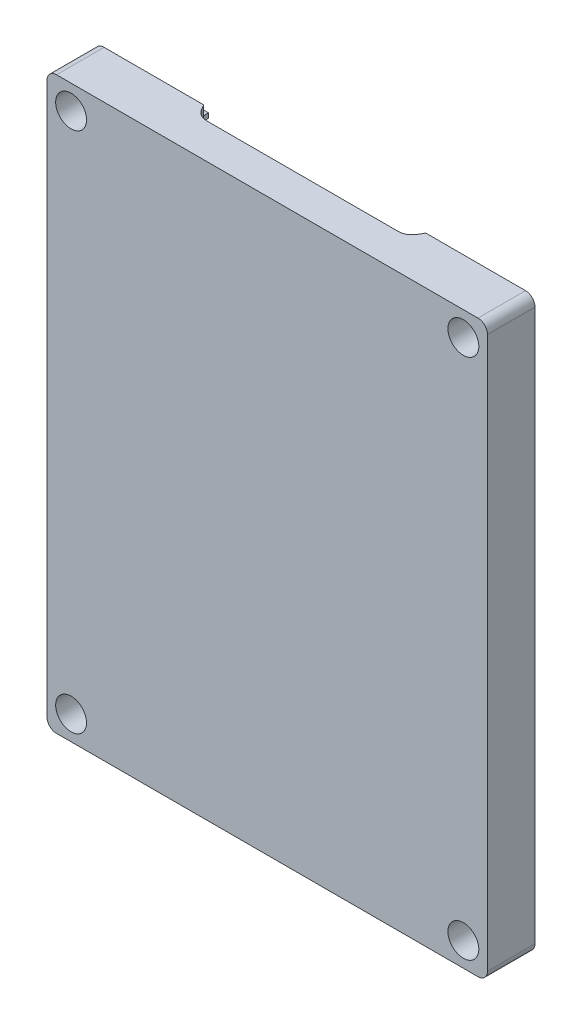
SolidWorks part; units mm, degrees
note: The reader was unsure of these and kept them because the rebuilt part matched: shared geometry of "Esquisse1<5>".
material "ABS"
ref_plane "Plan de face" through (0, 0, 0) normal (0, 0, 1) x (1, 0, 0)
ref_plane "Plan de dessus" through (0, 0, 0) normal (0, 1, 0) x (1, 0, 0)
ref_plane "Plan de droite" through (0, 0, 0) normal (1, 0, 0) x (0, 0, -1)
sketch "Esquisse1" plane through (0, 0, 0) normal (0, 0, 1) x (1, 0, 0)
  line L10 (-44.32, 60.43) -> (44.32, 60.43)
  line L11 (32.37, 58.48) -> (-32.37, 58.48)
  line L12 (-43.37, 46.0658) -> (-31.9558, 57.48)
  line L13 (31.9558, 57.48) -> (-31.9558, 57.48)
  line L14 (31.9558, 57.48) -> (43.37, 46.0658)
  line L15 (43.37, 46.0658) -> (43.37, -45.1658)
  line L21 (43.37, -45.1658) -> (31.9558, -56.58)
  line L26 (31.9558, -56.58) -> (-31.9558, -56.58)
  line L28 (-31.9558, -56.58) -> (-43.37, -45.1658)
  line L48 (-43.37, -45.1658) -> (-43.37, 46.0658)
  line L55 (-23.35, 60.43) -> (-44.32, 60.43)
  line L56 (-46.32, 58.43) -> (-46.32, -57.53)
  line L57 (-44.32, -59.53) -> (44.32, -59.53)
  line L58 (46.32, -57.53) -> (46.32, 58.43)
  line L59 (44.32, 60.43) -> (23.35, 60.43)
  line L64 (23.35, 60.43) -> (23.35, 58.48)
  line L65 (23.35, 58.48) -> (32.37, 58.48)
  line L66 (32.37, 58.48) -> (44.37, 46.48)
  line L67 (44.37, 46.48) -> (44.37, -45.58)
  line L68 (44.37, -45.58) -> (32.37, -57.58)
  line L69 (32.37, -57.58) -> (-32.37, -57.58)
  line L70 (-32.37, -57.58) -> (-44.37, -45.58)
  line L71 (-44.37, -45.58) -> (-44.37, 46.48)
  line L72 (-44.37, 46.48) -> (-32.37, 58.48)
  line L73 (-32.37, 58.48) -> (-23.35, 58.48)
  line L74 (-23.35, 58.48) -> (-23.35, 60.43)
  line L76 (-46.32, 58.43) -> (-46.32, -57.53)
  line L77 (-44.32, -59.53) -> (44.32, -59.53)
  line L78 (46.32, -57.53) -> (46.32, 58.43)
  line L82 (32.37, 58.48) -> (44.37, 46.48)
  line L83 (44.37, 46.48) -> (44.37, -45.58)
  line L84 (44.37, -45.58) -> (32.37, -57.58)
  line L85 (32.37, -57.58) -> (-32.37, -57.58)
  line L86 (-32.37, -57.58) -> (-44.37, -45.58)
  line L87 (-44.37, -45.58) -> (-44.37, 46.48)
  line L88 (-44.37, 46.48) -> (-32.37, 58.48)
  circle A1 centre (-41.2488, -54.4588) radius 1.6 construction
  circle A3 centre (41.2488, -54.4588) radius 1.6 construction
  arc A12 (-44.32, 60.43) -> (-46.32, 58.43) centre (-44.32, 58.43) ccw
  arc A13 (-46.32, -57.53) -> (-44.32, -59.53) centre (-44.32, -57.53) ccw
  arc A18 (44.32, -59.53) -> (46.32, -57.53) centre (44.32, -57.53) ccw
  arc A19 (46.32, 58.43) -> (44.32, 60.43) centre (44.32, 58.43) ccw
  arc A20 (-44.32, 60.43) -> (-46.32, 58.43) centre (-44.32, 58.43) ccw
  arc A21 (-46.32, -57.53) -> (-44.32, -59.53) centre (-44.32, -57.53) ccw
  arc A22 (44.32, -59.53) -> (46.32, -57.53) centre (44.32, -57.53) ccw
  arc A23 (46.32, 58.43) -> (44.32, 60.43) centre (44.32, 58.43) ccw
  circle A25 centre (41.2488, 55.3588) radius 1.6 construction
  circle A27 centre (-41.2488, 55.3588) radius 1.6 construction
  circle A29 centre (-41.2488, -54.4588) radius 1.6
  circle A31 centre (41.2488, -54.4588) radius 1.6
  circle A33 centre (41.2488, 55.3588) radius 1.6
  circle A35 centre (-41.2488, 55.3588) radius 1.6
  dimension "D1" = 0
  dimension "D2" = 1
extrude "Walls" add sketch "Esquisse1" along normal blind 10
extrude "Centrage" add sketch "Esquisse1<5>" against normal blind 1 contours L88 L87 L86 L85 L84 L83 L82 L11 L28 L48 L12 L13 L14 L15 L21 L26
sketch "Esquisse1<5>" plane through (0, 0, 0) normal (0, 0, 1) x (1, 0, 0) same geometry as "Esquisse1"
sketch "Esquisse2" plane through (0, 60.43, 0) normal (0, 1, 0) x (1, 0, 0)
  line L1 (-23.35, -2.6) -> (23.35, -2.6) construction
  line L2 (-23.35, -2.6) -> (-23.35, 1) construction
  line L3 (-23.35, 1) -> (23.35, 1)
  line L4 (23.35, -2.6) -> (23.35, 1) construction
  line L6 (-23.35, 0) -> (-22.72, -1.1)
  line L7 (-32.37, 0) -> (32.37, 0) construction
  line L8 (-23.35, 0) -> (-23.35, 1)
  line L9 (0, -6.05) -> (0, 6.05) construction
  line L10 (23.35, 0) -> (22.72, -1.1)
  line L11 (23.35, 0) -> (23.35, 1)
  line L12 (-20.12, -2.6) -> (20.12, -2.6)
  line L13 (-44.32, 0) -> (44.32, 0) construction
  line L20 (32.37, 1) -> (-32.37, 1) construction
  arc A0 (-22.72, -1.1) -> (-20.12, -2.6) centre (-20.1219, 0.4) ccw
  arc A1 (22.72, -1.1) -> (20.12, -2.6) centre (20.1219, 0.4) cw
  point P6 (0, -2.6)
  dimension "D5" = 3
  dimension "D1" = 46.7
  dimension "D2" = 2.6
  dimension "D3" = 1.1
  dimension "D4" = 0.63
  dimension "D6" = 3.23
extrude "Passage_CMC" cut sketch "Esquisse2" against normal up to next
sketch "Esquisse4" plane through (0, 0, 10) normal (0, 0, 1) x (1, 0, 0)
  line L8 (-43.37, -45.1658) -> (-43.37, 46.0658)
  line L9 (-31.9558, -56.58) -> (-43.37, -45.1658)
  line L10 (31.9558, -56.58) -> (-31.9558, -56.58)
  line L11 (43.37, -45.1658) -> (31.9558, -56.58)
  line L12 (43.37, 46.0658) -> (43.37, -45.1658)
  line L13 (31.9558, 57.48) -> (43.37, 46.0658)
  line L14 (-31.9558, 57.48) -> (31.9558, 57.48)
  line L15 (-43.37, 46.0658) -> (-31.9558, 57.48)
  line L16 (-43.37, -45.1658) -> (-43.37, 46.0658) construction
  line L17 (-43.37, 46.0658) -> (-31.9558, 57.48) construction
extrude "Couvercle" add sketch "Esquisse4" against normal blind 2
sketch "Esquisse5" plane through (0, 0, 10) normal (0, 0, 1) x (1, 0, 0)
  line L0 (-41.2488, 55.3588) -> (-41.2488, 60.43) construction
  line L2 (-41.2488, 55.3588) -> (-46.32, 55.3588) construction
  line L4 (-41.2488, 55.3588) -> (-37.6629, 51.7729) construction
  line L8 (-43.37, 46.0658) -> (-31.9558, 57.48) construction
  line L9 (-44.32, 60.43) -> (44.32, 60.43) construction
  line L10 (-46.32, 58.43) -> (-46.32, -57.53) construction
  line L11 (-41.2488, -54.4588) -> (-37.6629, -50.8729) construction
  line L12 (-31.9558, -56.58) -> (-43.37, -45.1658) construction
  line L13 (-41.2488, -54.4588) -> (-46.32, -54.4588) construction
  line L14 (-41.2488, -54.4588) -> (-41.2488, -59.53) construction
  line L15 (-44.32, -59.53) -> (44.32, -59.53) construction
  line L16 (0, -6.05) -> (0, 6.05) construction
  circle A0 centre (-41.2488, 55.3588) radius 1.6
  circle A5 centre (-41.2488, -54.4588) radius 1.6
  circle A6 centre (41.2488, 55.3588) radius 1.6
  circle A7 centre (41.2488, -54.4588) radius 1.6
  circle A8 centre (-41.2488, -54.4588) radius 3.25
  circle A9 centre (-41.2488, 55.3588) radius 3.25
  circle A10 centre (41.2488, 55.3588) radius 3.25
  circle A11 centre (41.2488, -54.4588) radius 3.25
  dimension "D1" = 3.2
  dimension "D2" = 6.5
extrude "Passage_M3" cut sketch "Esquisse5" against normal blind 5
